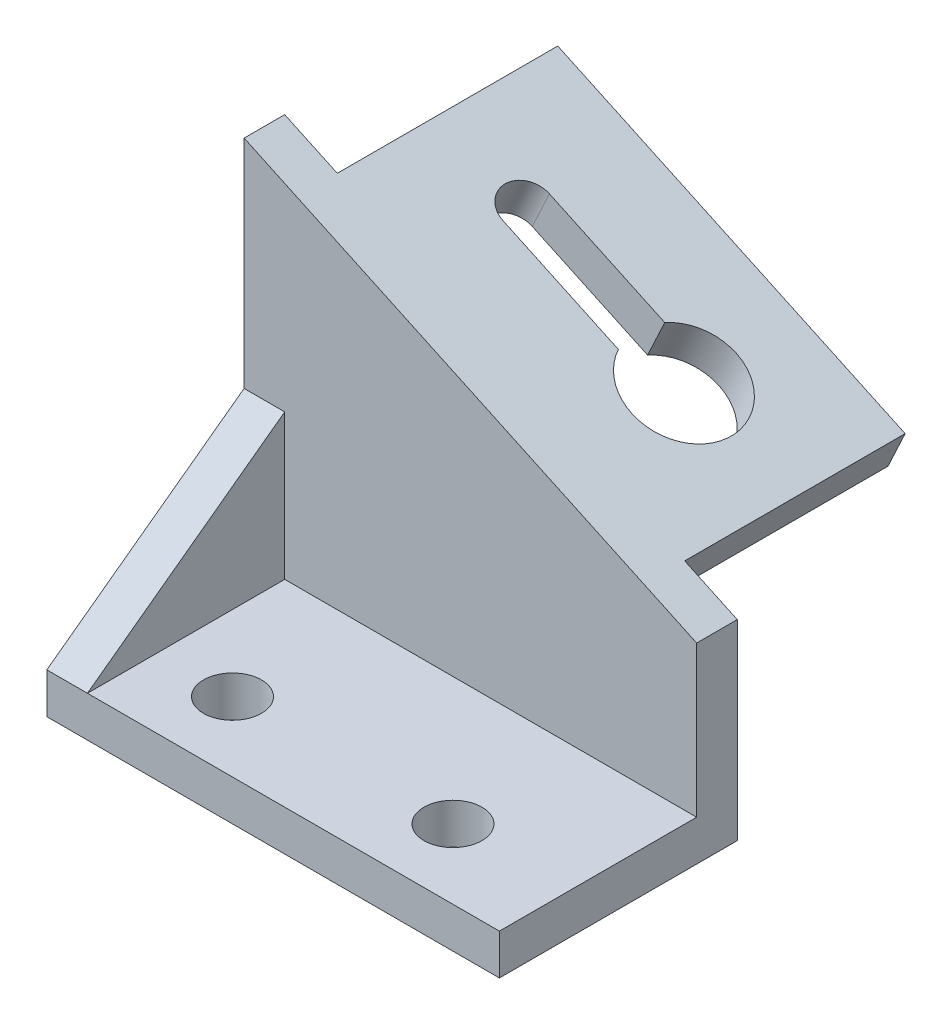
SolidWorks part; units mm, degrees
ref_plane "Front Plane" through (0, 0, 0) normal (0, 0, 1) x (1, 0, 0)
ref_plane "Top Plane" through (0, 0, 0) normal (0, 1, 0) x (1, 0, 0)
ref_plane "Right Plane" through (0, 0, 0) normal (1, 0, 0) x (0, 0, -1)
sketch "Sketch1" plane through (0, 0, 0) normal (0, 0, 1) x (1, 0, 0)
  line L0 (78, 33) -> (0, 69.372)
  line L1 (0, 0) -> (78, 0)
  line L2 (0, 0) -> (0, 69.372)
  line L4 (78, 0) -> (78, 33)
  dimension "D1" = 33
  dimension "D2" = 78
  dimension "D3" = 25
extrude "Boss-Extrude1" add sketch "Sketch1" against normal blind 79
sketch "Sketch2" plane through (78, 0, 0) normal (1, 0, 0) x (0, 0, -1)
  line L0 (0, 7) -> (34, 32)
  line L1 (0, 69.372) -> (34, 69.372)
  line L2 (0, 69.372) -> (0, 7)
  line L3 (0, 7) -> (34, 7)
  line L4 (34, 69.372) -> (34, 7)
  line L5 (79, 0) -> (0, 0) construction
  line M2 (0, 33) -> (0, 0)
  line M5 (79, 33) -> (0, 33)
  dimension "D1" = 34
  dimension "D2" = 25
  dimension "D3" = 7
extrude "Cut-Extrude1" cut sketch "Sketch2" against normal offset from surface (71 mm away) 7 contours L4 L0 M5 M2 | L4 L1 L2 M5 | L4 L0 L3 region at (78, 24.321, -11.7531) region at (78, 15.3333, -22.6667) region at (78, 51.186, -17) up to face at (0, 34.686, -39.5)
extrude "Cut-Extrude2" cut sketch "Sketch2<4>" against normal through all contours L4 L1 L2 M5 | L4 L0 M5 M2 region at (78, 24.321, -11.7531) region at (78, 51.186, -17)
sketch "Sketch2<4>" plane through (78, 0, 0) normal (1, 0, 0) x (0, 0, -1) same geometry as "Sketch2"
sketch "Sketch3" plane through (26.571, 56.9817, 0) normal (0.4226, 0.9063, 0) x (0.9063, -0.4226, 0)
  line L1 (-19.3179, 79) -> (46.7456, 79)
  line L2 (-19.3179, 79) -> (-19.3179, 41)
  line L3 (-19.3179, 41) -> (46.7456, 41)
  line L4 (46.7456, 79) -> (46.7456, 41)
  line L5 (-29.3179, 34) -> (56.7456, 34) construction
  line L6 (-29.3179, 79) -> (-29.3179, 34) construction
  line L7 (13.7139, 34) -> (13.7139, 55) construction
  line L8 (56.7456, 79) -> (-29.3179, 79) construction
  line L9 (-19.3179, 41) -> (-29.3179, 41)
  line L10 (-29.3179, 41) -> (98.2061, 41)
  line L12 (98.2061, 41) -> (98.2061, 79)
  line L13 (98.2061, 79) -> (-29.3179, 79)
  line L14 (-29.3179, 79) -> (-29.3179, 41)
  line L15 (-19.3179, 59) -> (-7.2544, 59) construction
  line L16 (46.7456, 59) -> (35.7456, 59) construction
  line L17 (13.7139, 63) -> (13.7139, 79) construction
  line L18 (35.7456, 59) -> (46.7456, 59) construction
  line L19 (-3.2544, 63) -> (18.6833, 63)
  line L21 (-3.2544, 55) -> (18.6833, 55)
  arc A0 (-3.2544, 63) -> (-3.2544, 55) centre (-3.2544, 59) ccw
  arc A1 (18.6833, 55) -> (18.6833, 63) centre (26.7456, 59) ccw
  point P30 (0, 0)
  point P31 (0, 0)
  line M3 (-29.3179, 79) -> (-29.3179, 34)
  line M5 (56.7456, 34) -> (56.7456, 79)
  line M6 (56.7456, 79) -> (-29.3179, 79)
  dimension "D3" = 8
  dimension "D6" = 18
  dimension "D7" = 20
  dimension "D1" = 7
  dimension "D2" = 10
  dimension "D8" = 20
extrude "Cut-Extrude3" cut sketch "Sketch3" against normal through all contours L9 L2 M6 M3 | L12 L13 L10 M5 | L4 L10 M5 M6 | A0 L21 A1 L19 region at (4.5315, 67.2589, -60) region at (73.4685, 35.1131, -60) region at (96.788, 24.239, -60)
sketch "Sketch4" plane through (42.3659, -19.7555, 0) normal (0.9063, -0.4226, 0) x (0, 0, -1)
  line L0 (41, 62.8724) -> (41, 32.9642) construction
  line L1 (41, 55.8724) -> (79, 55.8724)
  line L2 (41, 55.8724) -> (41, -8.5401)
  line L3 (41, -8.5401) -> (79, -8.5401)
  line L4 (79, 55.8724) -> (79, -8.5401)
  line L5 (79, 62.8724) -> (41, 62.8724) construction
  line L6 (79, 21.7978) -> (79, 62.8724) construction
  dimension "D1" = 7
extrude "Cut-Extrude4" cut sketch "Sketch4" against normal through all
sketch "Sketch5" plane through (0, 7, 0) normal (0, 1, 0) x (1, 0, 0)
  line L0 (0, 12) -> (78, 12) construction
  line L1 (0, 0) -> (0, 34) construction
  line L2 (78, 0) -> (78, 34) construction
  line L3 (7, 0) -> (78, 0) construction
  line L4 (39, 12) -> (39, 26.3322) construction
  circle A0 centre (20, 12) radius 5
  circle A1 centre (58, 12) radius 5
  dimension "D2" = 10
  dimension "D3" = 20
  dimension "D1" = 12
extrude "Cut-Extrude5" cut sketch "Sketch5" against normal through all
